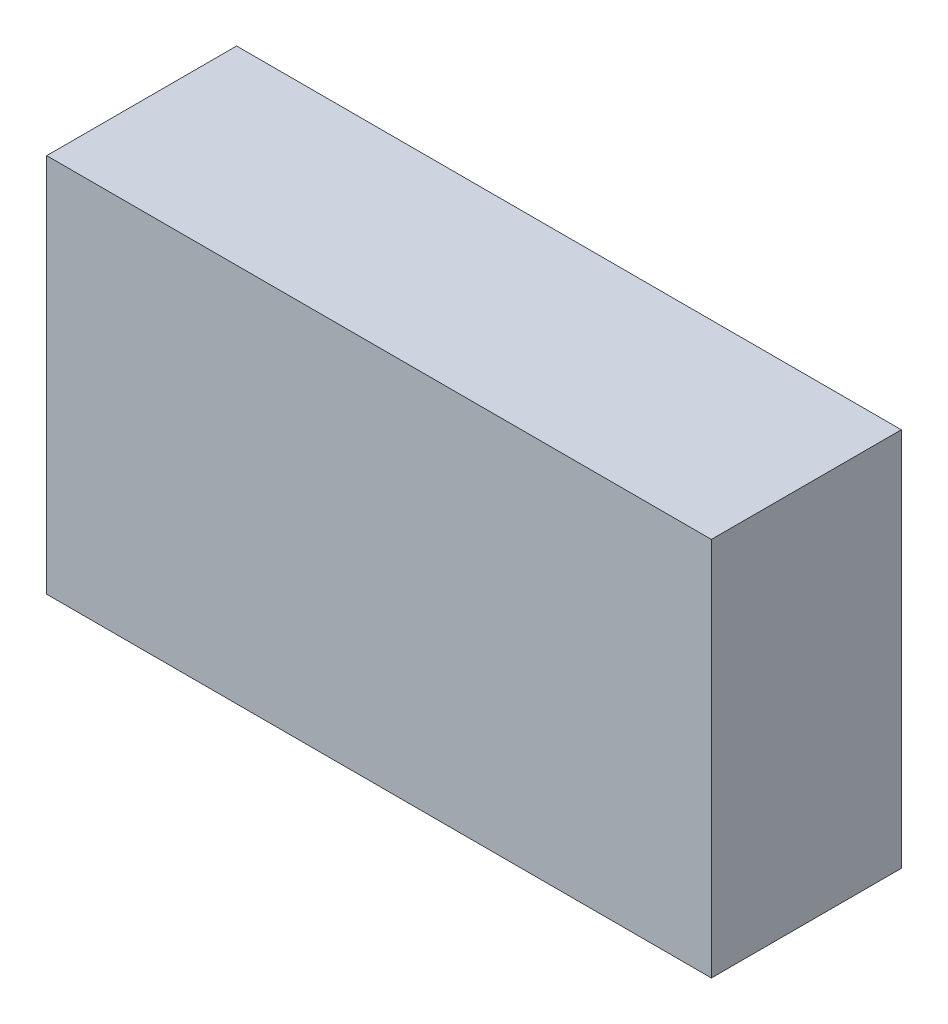
SolidWorks part; units mm, degrees
ref_plane "Front Plane" through (0, 0, 0) normal (0, 0, 1) x (1, 0, 0)
ref_plane "Top Plane" through (0, 0, 0) normal (0, 1, 0) x (1, 0, 0)
ref_plane "Right Plane" through (0, 0, 0) normal (1, 0, 0) x (0, 0, -1)
sketch "Sketch1" plane through (0, 0, 0) normal (0, 0, 1) x (1, 0, 0)
  line L1 (0, 0) -> (88.9, 0)
  line L2 (0, 0) -> (0, 50.8)
  line L3 (0, 50.8) -> (88.9, 50.8)
  line L4 (88.9, 0) -> (88.9, 50.8)
  dimension "D1" = 88.9
  dimension "D2" = 50.8
extrude "Boss-Extrude1" add sketch "Sketch1" along normal blind 25.4
